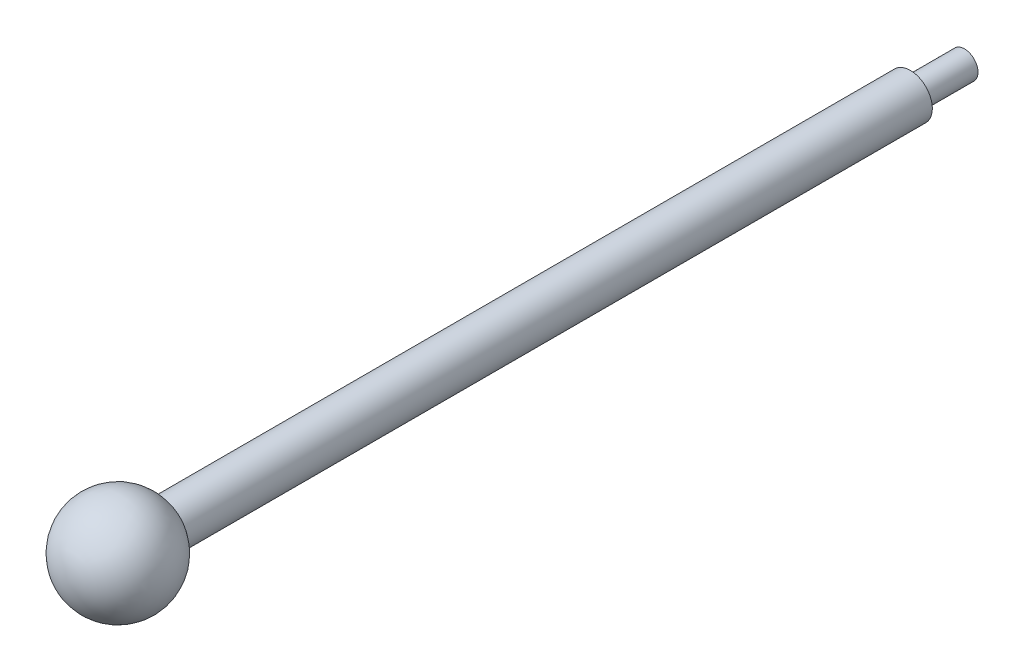
SolidWorks part; units mm, degrees
ref_plane "Płaszczyzna przednia" through (0, 0, 0) normal (0, 0, 1) x (1, 0, 0)
ref_plane "Płaszczyzna górna" through (0, 0, 0) normal (0, 1, 0) x (1, 0, 0)
ref_plane "Płaszczyzna prawa" through (0, 0, 0) normal (1, 0, 0) x (0, 0, -1)
sketch "Szkic1" plane through (0, 0, 0) normal (0, 0, 1) x (1, 0, 0)
  line L0 (0, 15) -> (0, -15)
  arc A2 (0, -15) -> (0, 15) centre (0, 0) cw
  dimension "D1" = 15
revolve "Obrót5" add sketch "Szkic1" angle 360 about L0
ref_plane "Płaszczyzna1" through (0, 0, -15) normal (0, 0, -1) x (-1, 0, 0)
sketch "Szkic2" plane through (0, 0, -15) normal (0, 0, -1) x (-1, 0, 0)
  circle A0 centre (0, 0) radius 6.5
  dimension "D1" = 13
extrude "Dodanie-wyciągnięcie1" add sketch "Szkic2" along normal blind 219 and the other way up to next contours A0
sketch "Szkic3" plane through (0, 0, -234) normal (0, 0, -1) x (-1, 0, 0)
  circle A0 centre (0, 0) radius 4
  dimension "D1" = 8
extrude "Dodanie-wyciągnięcie2" add sketch "Szkic3" along normal blind 16 contours A0
ref_plane "Płaszczyzna2" through (0, 6.5, 0) normal (0, 1, 0) x (1, 0, 0)
ref_axis "Oś1" through (0, 0, -13.5185) along (0, 0, -1)
